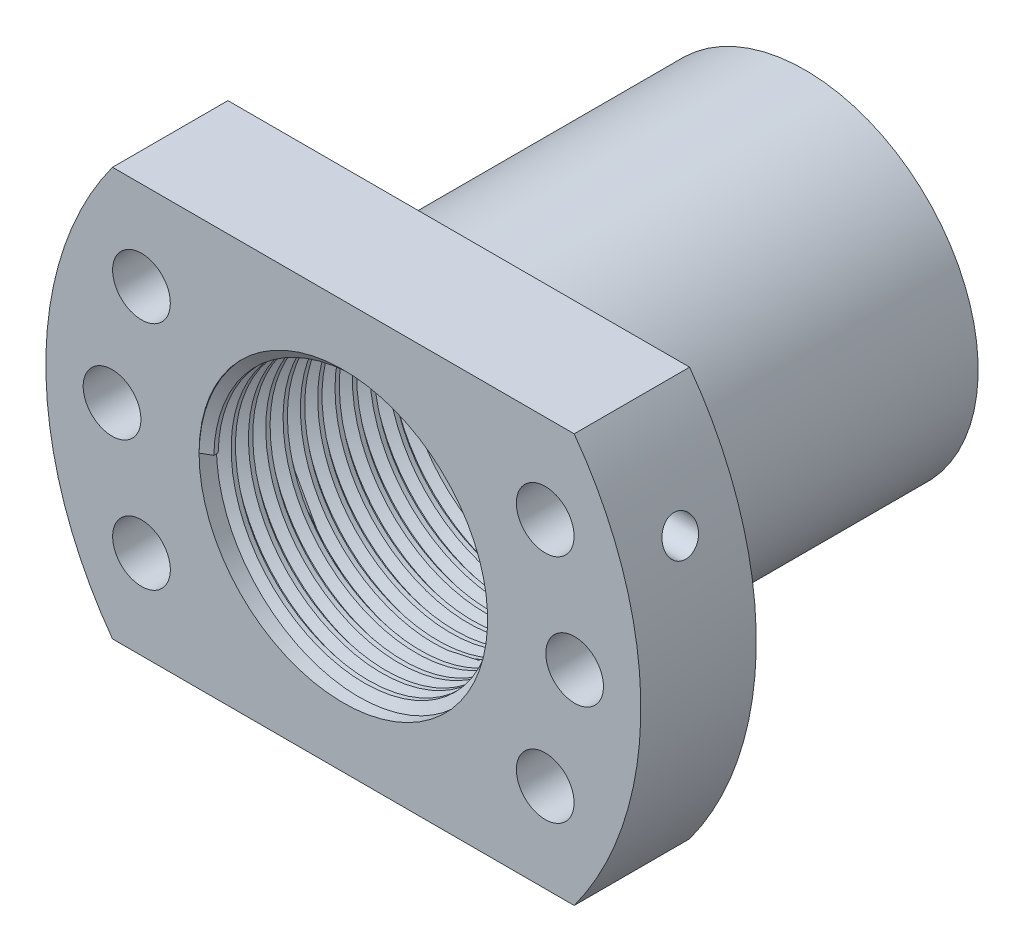
SolidWorks part; units mm, degrees
material "Cast Alloy Steel"
ref_plane "Front Plane" through (0, 0, 0) normal (0, 0, 1) x (1, 0, 0)
ref_plane "Top Plane" through (0, 0, 0) normal (0, 1, 0) x (1, 0, 0)
ref_plane "Right Plane" through (0, 0, 0) normal (1, 0, 0) x (0, 0, -1)
sketch "Sketch1" plane through (0, 0, 0) normal (0, 0, 1) x (1, 0, 0)
  line L1 (-20, -17.6953) -> (20, -17.6953)
  line L3 (-20, 17.6953) -> (20, 17.6953)
  line L5 (-20, -17.6953) -> (20, 17.6953) construction
  line L6 (-20, 17.6953) -> (20, -17.6953) construction
  arc A0 (-20, 17.6953) -> (-20, -17.6953) centre (4.2255, 0) ccw
  arc A1 (20, 17.6953) -> (20, -17.6953) centre (-4.2255, 0) cw
  point P0 (0, 0)
  dimension "D2" = 30
  dimension "D3" = 30
  dimension "D1" = 40
extrude "Boss-Extrude1" add sketch "Sketch1" against normal blind 10
sketch "Sketch2" plane through (0, 0, -10) normal (0, 0, -1) x (-1, 0, 0)
  circle A0 centre (0, 0) radius 15
  dimension "D1" = 30
extrude "Boss-Extrude2" add sketch "Sketch2" along normal blind 30
sketch "Sketch3" plane through (0, 0, 0) normal (0, 0, 1) x (1, 0, 0)
  circle A0 centre (0, 0) radius 12.5
  dimension "D1" = 25
extrude "Cut-Extrude1" cut sketch "Sketch3" against normal through all
thread "Thread1" pitch 1.5 method extrude profile "Thread Profile1" start angle 0, offset 0, length 38, pitch 1.5, diameter 25
ref_plane "Plane1" through (-12.5, 0, 0) normal (0, -1, 0) x (-1, 0, 0)
sketch "Thread Profile1" plane through (-12.5, 0, 0) normal (0, -1, 0) x (-1, 0, 0)
  line L0 (0, 0) -> (0, 1.5) construction
  line L11 (0, 0) -> (0, 1.3125)
  line L12 (0, 1.3125) -> (-0.8119, 0.8437)
  line L13 (-0.8119, 0.8437) -> (-0.8119, 0.4687)
  line L15 (-0.8119, 0.4687) -> (0, 0)
  line L17 (-0.8119, 0.6562) -> (0, 0.6562) construction
  point P2 (0, 0)
  dimension "Pitch" = 1.5
  dimension "Profile_Angle" = 60
  dimension "Profile_Land" = 0.375
  dimension "Profile_Height" = 0.8119
sketch "Sketch6" plane through (0, 0, 0) normal (0, 0, 1) x (1, 0, 0)
  line L0 (0, 0) -> (0, 9.448) construction
  line L1 (0, 9.448) -> (0, 0) construction
  line L2 (0, 0) -> (9.3162, 0) construction
  circle A0 centre (-17.4898, 10) radius 2.5
  circle A1 centre (-20.0385, 0) radius 2.5
  circle A2 centre (20.0385, 0) radius 2.5
  circle A3 centre (17.4898, 10) radius 2.5
  circle A4 centre (17.4898, -10) radius 2.5
  circle A5 centre (-17.4898, -10) radius 2.5
  dimension "D1" = 5
  dimension "D2" = 5
  dimension "D3" = 10
  dimension "D4" = 10
extrude "Cut-Extrude2" cut sketch "Sketch6" against normal blind 20
sketch "Sketch7" plane through (0, 0, 0) normal (1, 0, 0) x (0, 0, -1)
  circle A0 centre (5, 9.6139) radius 1.5
  dimension "D1" = 3
extrude "Cut-Extrude3" cut sketch "Sketch7" against normal through all both and the other way through all
